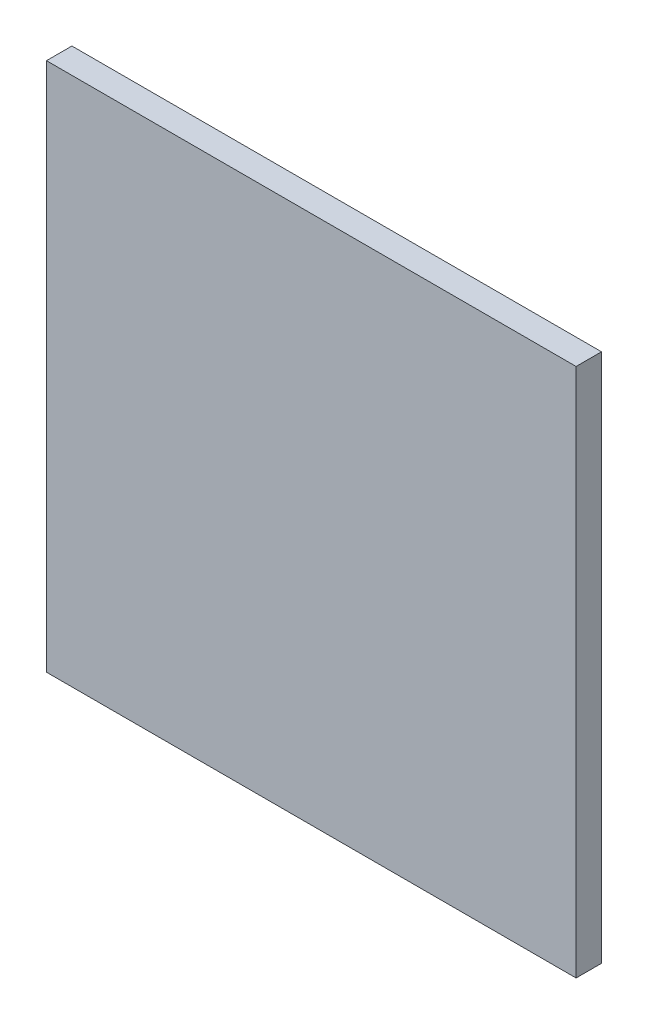
SolidWorks part; units mm, degrees
ref_plane "Front Plane" through (0, 0, 0) normal (0, 0, 1) x (1, 0, 0)
ref_plane "Top Plane" through (0, 0, 0) normal (0, 1, 0) x (1, 0, 0)
ref_plane "Right Plane" through (0, 0, 0) normal (1, 0, 0) x (0, 0, -1)
sketch "Sketch1" plane through (0, 0, 0) normal (0, 0, 1) x (1, 0, 0)
  line L1 (0, 0) -> (250, 0)
  line L2 (0, 0) -> (0, 250)
  line L3 (0, 250) -> (250, 250)
  line L4 (250, 0) -> (250, 250)
extrude "Boss-Extrude1" add sketch "Sketch1" along normal blind 12
